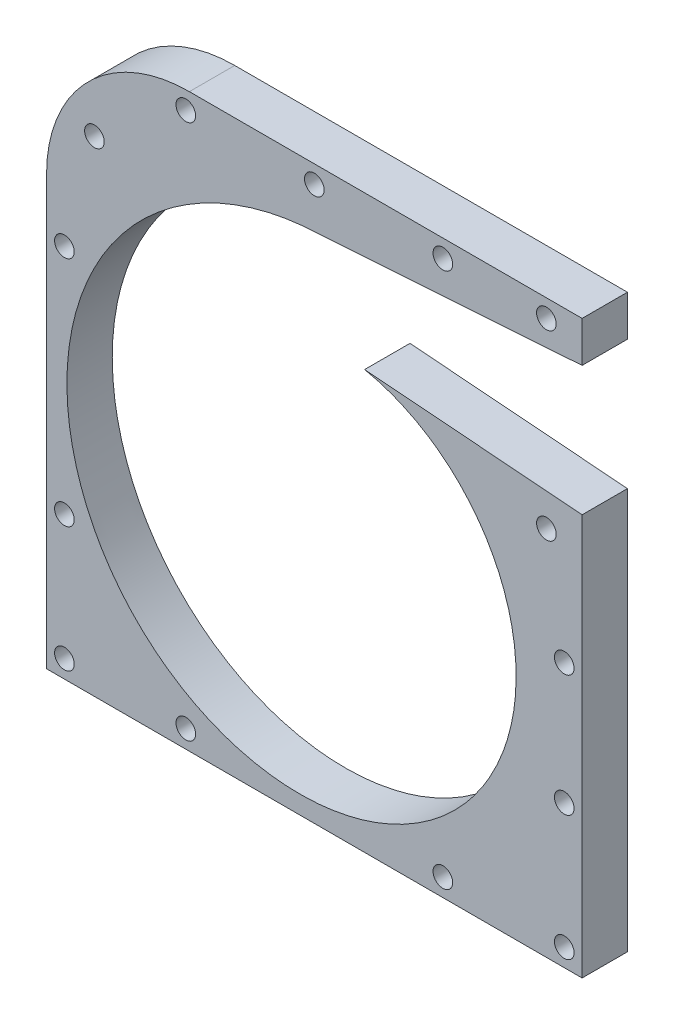
SolidWorks part; units mm, degrees
material "AISI 304"
ref_plane "Front Plane" through (0, 0, 0) normal (0, 0, 1) x (1, 0, 0)
ref_plane "Top Plane" through (0, 0, 0) normal (0, 1, 0) x (1, 0, 0)
ref_plane "Right Plane" through (0, 0, 0) normal (1, 0, 0) x (0, 0, -1)
sketch "Sketch1" plane through (0, 0, 0) normal (0, 0, 1) x (1, 0, 0)
  line L1 (-18.1818, -7.7823) -> (131.8182, -7.7823)
  line L2 (-18.1818, -7.7823) -> (-18.1818, 152.2177)
  line L3 (-18.1818, 152.2177) -> (131.8182, 152.2177)
  line L4 (131.8182, -7.7823) -> (131.8182, 152.2177)
  dimension "D1" = 160
  dimension "D2" = 150
extrude "Boss-Extrude1" add sketch "Sketch1" along normal blind 12.7
sketch "Sketch2" plane through (0, 0, 0) normal (0, 0, 1) x (1, 0, 0)
  line L0 (-18.1818, -7.7823) -> (131.8182, -7.7823) construction
  line L1 (56.8182, -7.7823) -> (56.8182, 152.2177) construction
  line L2 (131.8182, 152.2177) -> (-18.1818, 152.2177) construction
  line L3 (-18.1818, -7.7823) -> (131.8182, -7.7823) construction
  circle A0 centre (56.8182, 60.2177) radius 50 construction
  circle A1 centre (56.8182, 60.2177) radius 50.75
  point P0 (56.8182, 52.2686)
  dimension "D2" = 100
  dimension "D3" = 101.5
  dimension "D1" = 60.0509
  dimension "D4" = 68
extrude "Cut-Extrude2" cut sketch "Sketch2" along normal up to next
sketch "Sketch3" plane through (0, 0, 0) normal (0, 0, -1) x (-1, 0, 0)
  line L0 (-42.4775, -245.3976) -> (306.8559, -245.3976) construction
  line L1 (-107.6182, 60.2177) -> (-6.0182, 60.2177) construction
  line L3 (-130.5969, 104.5788) -> (-130.5969, 140.8094)
  line L4 (-130.5969, 104.5788) -> (-76.9549, 106.8017)
  circle A0 centre (-56.8182, 60.2177) radius 50.8 construction
  circle A1 centre (-56.8182, 60.2177) radius 50.75 construction
  circle A2 centre (-56.8182, 60.2177) radius 50.75
  point P5 (-76.9549, 106.8017)
  point P6 (-120.0714, 60.0509)
  point P9 (-63.5, -2.7792)
  point P10 (20.4545, 64.0852)
  point P13 (5.2437, 60.0509)
  point P14 (-63.5, 134.174)
  point P15 (-130.5969, 140.8094)
  point P16 (-130.5969, 104.5788)
  dimension "D1" = 101.6
sketch "Sketch5" plane through (0, 0, 0) normal (0, 0, 1) x (1, 0, 0)
  circle A0 centre (56.8182, 60.2177) radius 51.1201
curve "Helix/Spiral2"
sketch "Sketch8" plane through (0, 0, 12.7) normal (0, 0, 1) x (1, 0, 0)
  line L0 (58.9317, 135.8843) -> (131.8182, 140.8094)
  line L1 (131.8182, 140.8094) -> (131.8182, 104.5788)
  line L2 (131.8182, 104.5788) -> (70.9088, 109.3575)
  line L3 (131.8182, -7.7823) -> (131.8182, 152.2177) construction
  spline S0 degree 3 poles (1651.8411, -1079.5367) (-229.7192, -143.5522) (-21.1382, 148.1207) (83.2388, 105.2908) (86.1686, 103.7524) (91.7235, 100.1208) (94.3486, 98.0276) (99.1887, 93.3472) (101.4036, 90.76) (105.3304, 85.1727) (107.0421, 82.1726) (109.8854, 75.8577) (111.0169, 72.5431) (112.6419, 65.712) (113.1355, 62.1958) (113.449, 55.0847) (113.269, 51.4901) (112.2238, 44.352) (111.3586, 40.8087) (108.9564, 33.9042) (107.4194, 30.5432) (103.7119, 24.1311) (101.5416, 21.0801) (96.6303, 15.4078) (93.8895, 12.7866) (87.9227, 8.0805) (84.6968, 5.9958) (77.8655, 2.4525) (74.2601, 0.9941) (66.7916, -1.2278) (62.9287, -1.991) (55.0798, -2.7774) (51.0939, -2.8005) (43.1413, -2.0875) (39.1747, -1.3513) (31.4057, 0.8716) (27.6034, 2.3584) (20.3052, 6.0466) (16.8095, 8.248) (10.2591, 13.3019) (7.2045, 16.1545) (1.6578, 22.4224) (-0.8343, 25.8377) (-5.1525, 33.1198) (-6.9784, 36.9865) (-9.8828, 45.0414) (-10.9611, 49.2293) (-12.3142, 57.7818) (-12.5888, 62.1461) (-12.3065, 70.8967) (-11.7496, 75.2828) (-9.8061, 83.9183) (-8.4194, 88.1675) (-4.8487, 96.372) (-2.6646, 100.3271) (2.4392, 107.7936) (5.3588, 111.3049) (11.8435, 117.7469) (15.4084, 120.6775) (23.0682, 125.8397) (27.1629, 128.0712) (35.745, 131.7396) (40.2322, 133.1765) (177.9482, 163.235) (410.4015, -168.0858) (-1258.2145, -1322.1018) knots -1.015613 -1.015613 -1.015613 -1.015613 0.03125 0.03125 0.0625 0.0625 0.09375 0.09375 0.125 0.125 0.15625 0.15625 0.1875 0.1875 0.21875 0.21875 0.25 0.25 0.28125 0.28125 0.3125 0.3125 0.34375 0.34375 0.375 0.375 0.40625 0.40625 0.4375 0.4375 0.46875 0.46875 0.5 0.5 0.53125 0.53125 0.5625 0.5625 0.59375 0.59375 0.625 0.625 0.65625 0.65625 0.6875 0.6875 0.71875 0.71875 0.75 0.75 0.78125 0.78125 0.8125 0.8125 0.84375 0.84375 0.875 0.875 0.90625 0.90625 0.9375 0.9375 0.96875 0.96875 1.871775 1.871775 1.871775 1.871775 only from (70.9088, 109.3575) to (58.9317, 135.8843) construction
  spline S1 degree 3 poles (70.9088, 109.3575) (74.0669, 108.7182) (77.1879, 107.7737) (83.2388, 105.2908) (86.1686, 103.7524) (91.7235, 100.1208) (94.3486, 98.0276) (99.1887, 93.3472) (101.4036, 90.76) (105.3304, 85.1727) (107.0421, 82.1726) (109.8854, 75.8577) (111.0169, 72.5431) (112.6419, 65.712) (113.1355, 62.1958) (113.449, 55.0847) (113.269, 51.4901) (112.2238, 44.352) (111.3586, 40.8087) (108.9564, 33.9042) (107.4194, 30.5432) (103.7119, 24.1311) (101.5416, 21.0801) (96.6303, 15.4078) (93.8895, 12.7866) (87.9227, 8.0805) (84.6968, 5.9958) (77.8655, 2.4525) (74.2601, 0.9941) (66.7916, -1.2278) (62.9287, -1.991) (55.0798, -2.7774) (51.0939, -2.8005) (43.1413, -2.0875) (39.1747, -1.3513) (31.4057, 0.8716) (27.6034, 2.3584) (20.3052, 6.0466) (16.8095, 8.248) (10.2591, 13.3019) (7.2045, 16.1545) (1.6578, 22.4224) (-0.8343, 25.8377) (-5.1525, 33.1198) (-6.9784, 36.9865) (-9.8828, 45.0414) (-10.9611, 49.2293) (-12.3142, 57.7818) (-12.5888, 62.1461) (-12.3065, 70.8967) (-11.7496, 75.2828) (-9.8061, 83.9183) (-8.4194, 88.1675) (-4.8487, 96.372) (-2.6646, 100.3271) (2.4392, 107.7936) (5.3588, 111.3049) (11.8435, 117.7469) (15.4084, 120.6775) (23.0682, 125.8397) (27.1629, 128.0712) (35.745, 131.7396) (40.2322, 133.1765) (49.445, 135.1873) (54.1703, 135.7612) (58.9317, 135.8843) knots 0 0 0 0 0.03125 0.03125 0.0625 0.0625 0.09375 0.09375 0.125 0.125 0.15625 0.15625 0.1875 0.1875 0.21875 0.21875 0.25 0.25 0.28125 0.28125 0.3125 0.3125 0.34375 0.34375 0.375 0.375 0.40625 0.40625 0.4375 0.4375 0.46875 0.46875 0.5 0.5 0.53125 0.53125 0.5625 0.5625 0.59375 0.59375 0.625 0.625 0.65625 0.65625 0.6875 0.6875 0.71875 0.71875 0.75 0.75 0.78125 0.78125 0.8125 0.8125 0.84375 0.84375 0.875 0.875 0.90625 0.90625 0.9375 0.9375 0.96875 0.96875 1 1 1 1
extrude "Cut-Extrude3" cut sketch "Sketch8" against normal up to next
fillet "Fillet1" radius 40 1 edges at (-18.1818, 152.2177, 6.35)
sketch "Sketch9" plane through (0, 0, 12.7) normal (0, 0, 1) x (1, 0, 0)
  line L0 (131.8182, 140.8094) -> (131.8182, 152.2177) construction
  line L1 (126.8182, 152.2177) -> (126.8182, -7.7823) construction
  line L2 (131.8182, 152.2177) -> (21.8182, 152.2177) construction
  line L3 (-18.1818, -7.7823) -> (131.8182, -7.7823) construction
  line L4 (131.8182, -7.7823) -> (131.8182, 104.5788) construction
  circle A1 centre (121.8182, 147.2177) radius 2.75
  circle A3 centre (92.8182, 147.2177) radius 2.75
  circle A5 centre (56.8182, 147.2177) radius 2.75
  circle A6 centre (20.8182, 147.2177) radius 2.75
  circle A7 centre (-4.7746, 128.0936) radius 2.75
  circle A8 centre (-13.1818, 97.2177) radius 2.75
  circle A9 centre (-13.1818, 32.2177) radius 2.75
  circle A10 centre (-13.1818, -2.7823) radius 2.75
  circle A11 centre (20.8182, -2.7823) radius 2.75
  circle A12 centre (92.8182, -2.7823) radius 2.75
  circle A13 centre (126.8182, -2.7823) radius 2.75
  circle A14 centre (126.8182, 32.2177) radius 2.75
  circle A15 centre (126.8182, 66.2177) radius 2.75
  circle A16 centre (121.8182, 96.2177) radius 2.75
  dimension "D11" = 10
  dimension "D2" = 29
  dimension "D3" = 36
  dimension "D4" = 31.9488
  dimension "D5" = 32
  dimension "D6" = 35
  dimension "D7" = 34
  dimension "D8" = 34
  dimension "D9" = 35
  dimension "D10" = 34
  dimension "D12" = 36
  dimension "D13" = 5
  dimension "D14" = 30
  dimension "D15" = 10
extrude "Cut-Extrude4" cut sketch "Sketch9" against normal up to next
